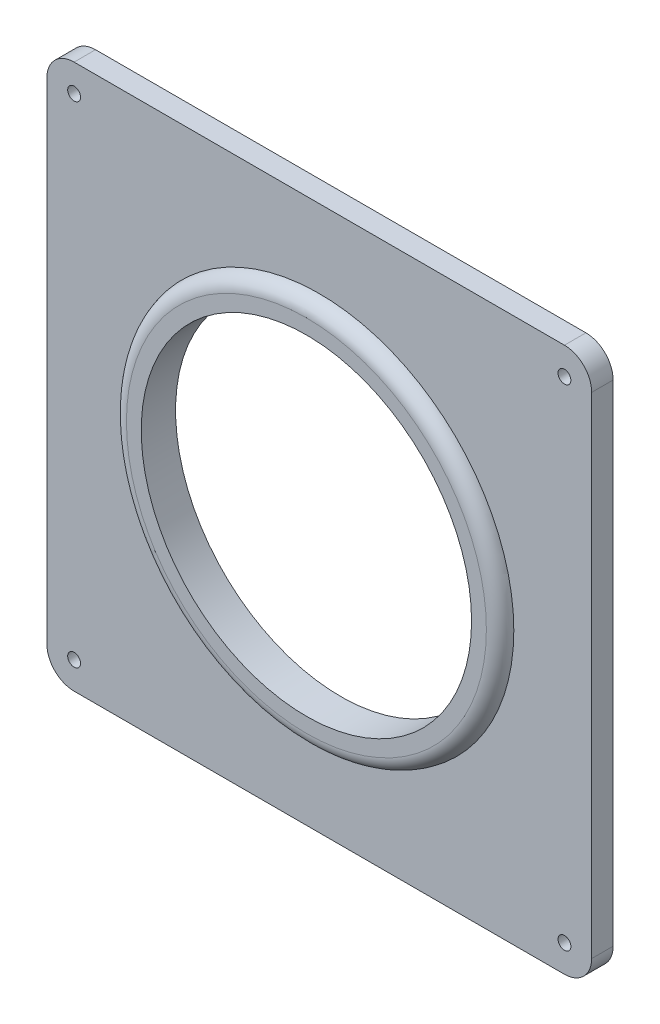
SolidWorks part; units mm, degrees
ref_plane "Front Plane" through (0, 0, 0) normal (0, 0, 1) x (1, 0, 0)
ref_plane "Top Plane" through (0, 0, 0) normal (0, 1, 0) x (1, 0, 0)
ref_plane "Right Plane" through (0, 0, 0) normal (1, 0, 0) x (0, 0, -1)
sketch "Sketch1" plane through (0, 0, 0) normal (0, 0, 1) x (1, 0, 0)
  line L1 (-63.5, -63.5) -> (-63.5, 63.5)
  line L2 (-60.5, -60.5) -> (60.5, -60.5)
  line L3 (-60.5, -60.5) -> (-60.5, 60.5)
  line L4 (-60.5, 60.5) -> (60.5, 60.5)
  line L5 (60.5, -60.5) -> (60.5, 60.5)
  line L6 (-60.5, -60.5) -> (60.5, 60.5) construction
  line L7 (-60.5, 60.5) -> (60.5, -60.5) construction
  line L8 (-63.5, 63.5) -> (63.5, 63.5)
  line L9 (63.5, -63.5) -> (63.5, 63.5)
  line L10 (-63.5, -63.5) -> (63.5, -63.5)
  circle A0 centre (0, 0) radius 44.45 construction
  circle A1 centre (0, 0) radius 38.5
  circle A2 centre (0, 0) radius 60.5 construction
  dimension "D1" = 88.9
  dimension "D2" = 77
  dimension "D3" = 121
  dimension "D4" = 3
sketch "Sketch2" plane through (0, 0, 0) normal (1, 0, 0) x (0, 0, -1)
  line L0 (0, 0) -> (22.225, 38.4948) construction
  line L1 (0, 0) -> (-17.0754, 0) construction
  line L2 (0, 0) -> (22.225, -38.4948) construction
  line L4 (22.225, 38.4948) -> (0, 38.4948) construction
  line L5 (0, 44.45) -> (0, -44.45) construction
  circle A0 centre (0, 0) radius 44.45 construction
  point P3 (0, 44.45)
  dimension "D1" = 88.9
  dimension "D2" = 120
extrude "Boss-Extrude1" add sketch "Sketch1" along normal blind 5 contours L1 L10 L9 L8 L5 L2 L3 L4 | L2 L5 L4 L3 A1 region at (-61.7039, 0, 0) region at (-58.7888, 0, 0)
sketch "Sketch3" plane through (0, 0, 5) normal (0, 0, 1) x (1, 0, 0)
  circle A0 centre (0, 0) radius 45.35
  circle A1 centre (0, 0) radius 38.5 construction
  circle A2 centre (0, 0) radius 38.5
  dimension "D1" = 6.85
  dimension "D2" = 6.85
extrude "Boss-Extrude2" add sketch "Sketch3" along normal blind 3
fillet "Fillet1" radius 6.35 4 edges at (63.5, 63.5, 2.5) (63.5, -63.5, 2.5) (-63.5, -63.5, 2.5) (-63.5, 63.5, 2.5)
fillet "Fillet2" radius 3.425 1 edges at (45.35, 0, 8)
sketch "Sketch5" plane through (0, 0, 5) normal (0, 0, 1) x (1, 0, 0)
  line L0 (-1000, 0) -> (49000, 0) construction
  line L1 (0, -1000) -> (0, 0) construction
  circle A0 centre (-57.15, 57.15) radius 1.5
  circle A1 centre (57.15, 57.15) radius 1.5
  circle A2 centre (57.15, -57.15) radius 1.5
  circle A3 centre (-57.15, -57.15) radius 1.5
  point P5 (0, -20.5276)
  point P7 (-28.3805, 0)
  point P17 (30.5211, 0)
  dimension "D1" = 3
extrude "Cut-Extrude2" cut sketch "Sketch5" against normal through all contours A0 | A3 | A2 | A1 region at (-57.15, 57.15, 5) region at (57.15, 57.15, 5) region at (57.15, -57.15, 5) region at (-57.15, -57.15, 5)
